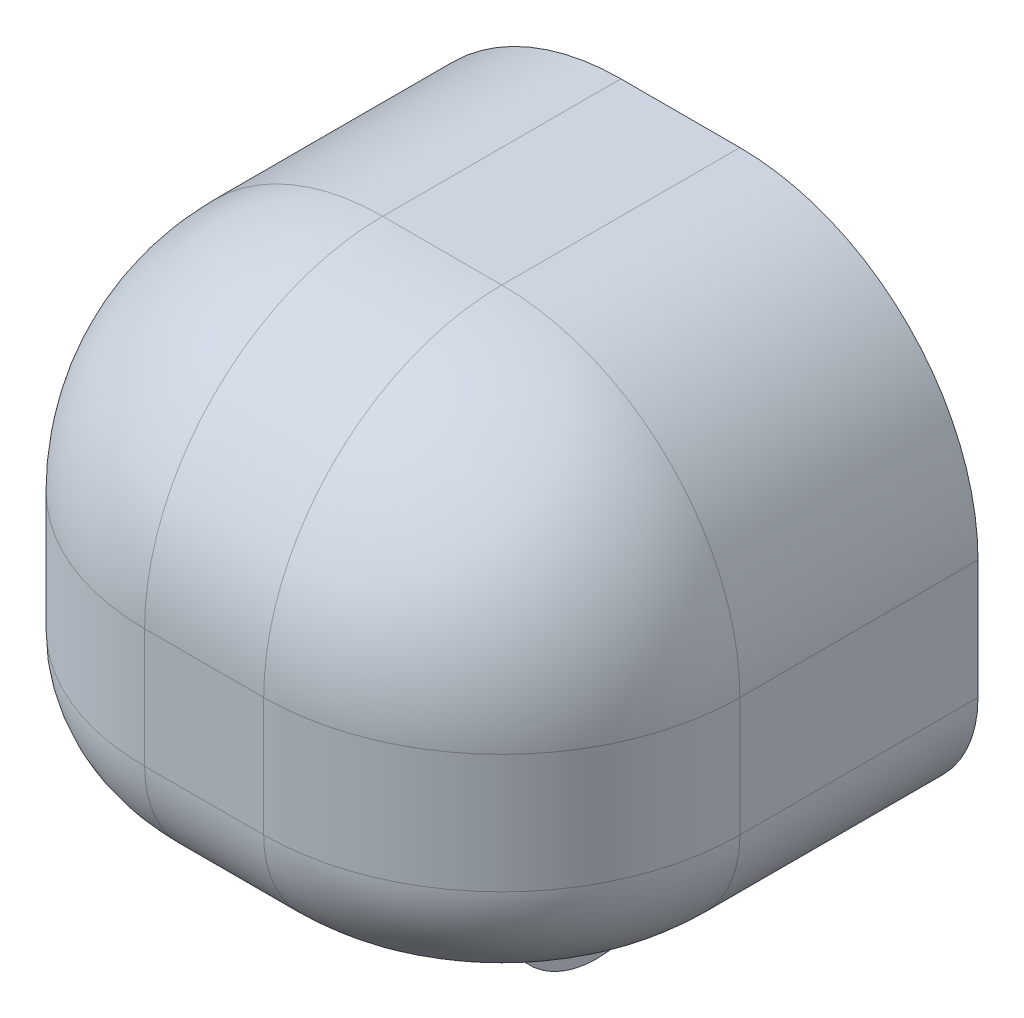
SolidWorks part; units mm, degrees
ref_plane "Front Plane" through (0, 0, 0) normal (0, 0, 1) x (1, 0, 0)
ref_plane "Top Plane" through (0, 0, 0) normal (0, 1, 0) x (1, 0, 0)
ref_plane "Right Plane" through (0, 0, 0) normal (1, 0, 0) x (0, 0, -1)
sketch "Sketch2" plane through (0, 0, 0) normal (0, 1, 0) x (1, 0, 0)
  line L1 (12.5, 12.5) -> (-12.5, 12.5)
  line L2 (12.5, 12.5) -> (12.5, -12.5)
  line L3 (12.5, -12.5) -> (-12.5, -12.5)
  line L4 (-12.5, 12.5) -> (-12.5, -12.5)
  line L5 (12.5, 12.5) -> (-12.5, -12.5) construction
  line L6 (12.5, -12.5) -> (-12.5, 12.5) construction
  point P0 (0, 0)
  dimension "D1" = 25
  dimension "D2" = 25
extrude "Boss-Extrude1" add sketch "Sketch2" along normal blind 25
fillet "Fillet2" radius 10 2 edges at (-12.5, 12.5, 12.5) (12.5, 12.5, 12.5)
fillet "Fillet3" radius 10 5 edges at (-12.5, 25, -5) (-9.5711, 25, 9.5711) (0, 25, 12.5) (12.5, 25, -5) (9.5711, 25, 9.5711)
sketch "Sketch3" plane through (0, 0, 0) normal (0, -1, 0) x (1, 0, 0)
  line L0 (-4, 4) -> (-4, -4)
  line L1 (3, 3) -> (-3, 3)
  line L2 (3, 3) -> (3, -3)
  line L3 (3, -3) -> (-3, -3)
  line L4 (-3, 3) -> (-3, -3)
  line L5 (3, 3) -> (-3, -3) construction
  line L6 (3, -3) -> (-3, 3) construction
  line L7 (4, -4) -> (-4, -4)
  line L8 (4, 4) -> (4, -4)
  line L9 (4, 4) -> (-4, 4)
  line L10 (-14, 14) -> (-14, -14)
  line L11 (14, -14) -> (-14, -14)
  line L12 (14, 14) -> (14, -14)
  line L13 (14, 14) -> (-14, 14)
  point P0 (0, 0)
  line M4 (2.5, 12.5) -> (-2.5, 12.5)
  arc M5 (-2.5, 12.5) -> (-12.5, 2.5) centre (-2.5, 2.5) ccw
  line M6 (-12.5, 2.5) -> (-12.5, -12.5)
  line M7 (-12.5, -12.5) -> (12.5, -12.5)
  line M8 (12.5, -12.5) -> (12.5, 2.5)
  arc M9 (12.5, 2.5) -> (2.5, 12.5) centre (2.5, 2.5) ccw
  dimension "D1" = 6
  dimension "D2" = 6
  dimension "D3" = 1
  dimension "D4" = 10
extrude "Cut-Extrude1" cut sketch "Sketch3" against normal blind 5 contours L9 L8 L7 L0 M9 M4 M5 M6 M7 M8 | L1 L4 L3 L2 region at (0, 0, 0) region at (9.3211, 0, 9.3211)
fillet "Fillet5" radius 5 5 edges at (12.5, 5, -5) (9.5711, 5, 9.5711) (0, 5, 12.5) (-9.5711, 5, 9.5711) (-12.5, 5, -5)
sketch "Sketch5" plane through (0, 0, 0) normal (0, -1, 0) x (1, 0, 0)
  line L0 (-3, 3) -> (-3, 4.7681)
  line L1 (-3, 4.7681) -> (3, 4.7681)
  line L2 (3, 4.7681) -> (3, -4.9058)
  line L3 (3, -4.9058) -> (-3, -4.9058)
  line L4 (-3, -4.9058) -> (-3, 3)
extrude "Cut-Extrude2" cut sketch "Sketch5" against normal blind 5
fillet "Fillet6" radius 4 4 edges at (3.5, 0, -4) (3.5, 0, 4) (-3.5, 0, -4) (-3.5, 0, 4)
sketch "Sketch6" plane through (-4, 0, 0) normal (-1, 0, 0) x (0, 0, 1)
  circle A0 centre (0, 3) radius 1.5
extrude "Cut-Extrude3" cut sketch "Sketch6" against normal blind 15
sketch "Sketch7" plane through (0, 0, -12.5) normal (0, 0, -1) x (-1, 0, 0)
  line L4 (-12.5, 15) -> (-12.5, 10)
  line L5 (-7.5, 5) -> (7.5, 5)
  line L6 (12.5, 10) -> (12.5, 15)
  line L7 (2.5, 25) -> (-2.5, 25)
  line L8 (-12.5, 15) -> (-12.5, 10)
  line L9 (-7.5, 5) -> (7.5, 5)
  line L10 (12.5, 10) -> (12.5, 15)
  line L11 (2.5, 25) -> (-2.5, 25)
  arc A4 (-12.5, 10) -> (-7.5, 5) centre (-7.5, 10) ccw
  arc A5 (7.5, 5) -> (12.5, 10) centre (7.5, 10) ccw
  arc A6 (12.5, 15) -> (2.5, 25) centre (2.5, 15) ccw
  arc A7 (-2.5, 25) -> (-12.5, 15) centre (-2.5, 15) ccw
  arc A8 (-12.5, 10) -> (-7.5, 5) centre (-7.5, 10) ccw
  arc A9 (7.5, 5) -> (12.5, 10) centre (7.5, 10) ccw
  arc A10 (12.5, 15) -> (2.5, 25) centre (2.5, 15) ccw
  arc A11 (-2.5, 25) -> (-12.5, 15) centre (-2.5, 15) ccw
  dimension "D1" = 0
extrude "Cut-Extrude4" cut sketch "Sketch7" against normal blind 5
